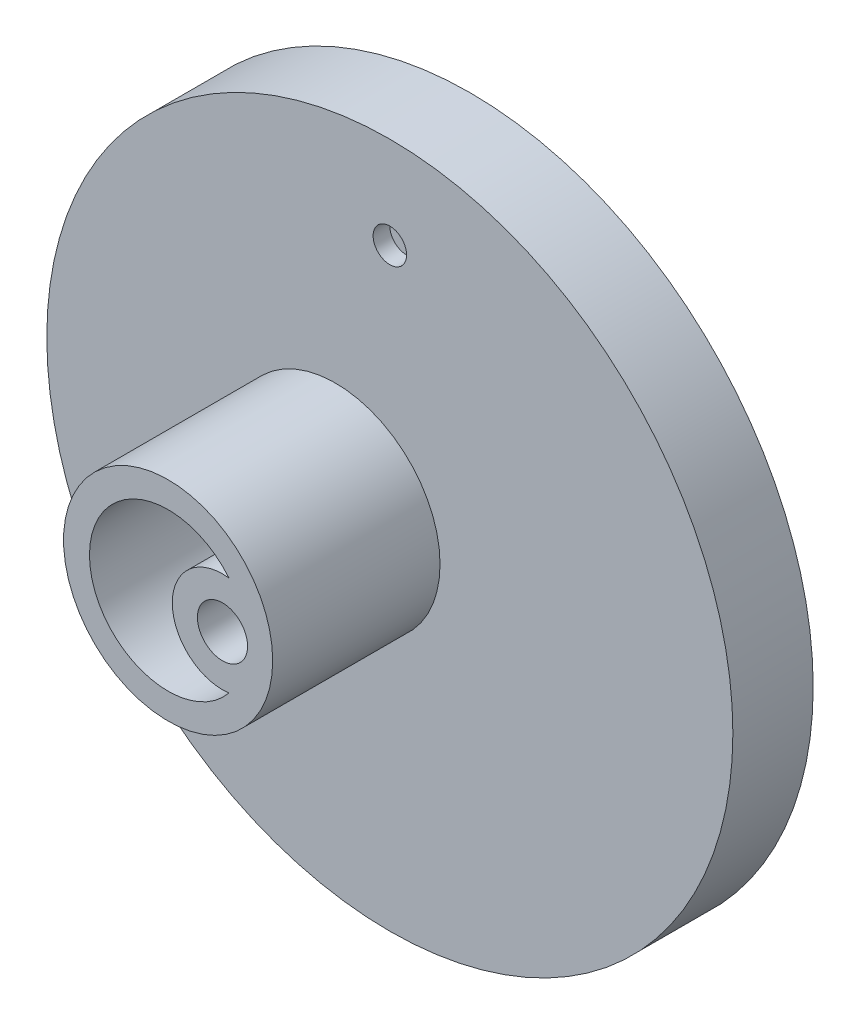
SolidWorks part; units mm, degrees
ref_plane "Plan de face" through (0, 0, 0) normal (0, 0, 1) x (1, 0, 0)
ref_plane "Plan de dessus" through (0, 0, 0) normal (0, 1, 0) x (1, 0, 0)
ref_plane "Plan de droite" through (0, 0, 0) normal (1, 0, 0) x (0, 0, -1)
sketch "Esquisse2" plane through (0, 0, 0) normal (0, 0, 1) x (1, 0, 0)
  circle A0 centre (0, 0) radius 20.5
  dimension "D1" = 41
extrude "Extrusion1" add sketch "Esquisse2" along normal blind 4.8
sketch "Esquisse3" plane through (0, 0, 4.8) normal (0, 0, 1) x (1, 0, 0)
  circle A0 centre (-3.25, 0) radius 6.25
  dimension "D1" = 12.5
extrude "Extrusion2" add sketch "Esquisse3" along normal blind 10
sketch "Esquisse4" plane through (0, 0, 14.8) normal (0, 0, 1) x (1, 0, 0)
  arc A0 (0.3888, 2.9747) -> (0.3888, -2.9747) centre (0, 0) ccw
  arc A1 (0.3888, 2.9747) -> (0.3888, -2.9747) centre (-3.25, 0) ccw
  dimension "D1" = 6
  dimension "D2" = 9.4
extrude "Enlèv. mat.-Extru.1" cut sketch "Esquisse4" against normal blind 10
sketch "Esquisse5" plane through (0, 0, 14.8) normal (0, 0, 1) x (1, 0, 0)
  circle A0 centre (0, 0) radius 1.5
  dimension "D1" = 3
extrude "Enlèv. mat.-Extru.2" cut sketch "Esquisse5" against normal through all
sketch "Esquisse6" plane through (0, 0, 0) normal (0, 0, -1) x (-1, 0, 0)
  circle A0 centre (0, 0) radius 6.4
  dimension "D1" = 12.8
extrude "Enlèv. mat.-Extru.3" cut sketch "Esquisse6" against normal blind 1.8
sketch "Esquisse7" plane through (0, 0, 4.8) normal (0, 0, 1) x (1, 0, 0)
  circle A0 centre (0, 15) radius 1
  dimension "D1" = 2
  dimension "D2" = 15
extrude "Enlèv. mat.-Extru.4" cut sketch "Esquisse7" against normal blind 1
sketch "Esquisse8" plane through (0, 0, 0) normal (0, 0, -1) x (-1, 0, 0)
  line L0 (-3.1909, 7.2269) -> (-7.7082, 15.051)
  line L1 (3.1909, 7.2269) -> (7.7082, 15.051)
  line L2 (0, 0) -> (0, 23.2146) construction
  line L3 (0, 0) -> (-13.6178, 23.5868) construction
  arc A0 (3.1909, 7.2269) -> (-3.1909, 7.2269) centre (0, 0) ccw
  arc A1 (7.7082, 15.051) -> (-7.7082, 15.051) centre (0, 0) ccw
  dimension "D1" = 33.82
  dimension "D2" = 15.8
  dimension "D3" = 60
  dimension "D4" = 1.7
extrude "Enlèv. mat.-Extru.5" cut sketch "Esquisse8" against normal blind 1.8
ref_axis "Axe1" through (0, 0, 21.4739) along (0, 0, -1)
pattern_circular "Répétition circulaire1" count 6 over 360 about axis through (0, 0, 21.4739) along (0, 0, -1) of "Enlèv. mat.-Extru.5"
